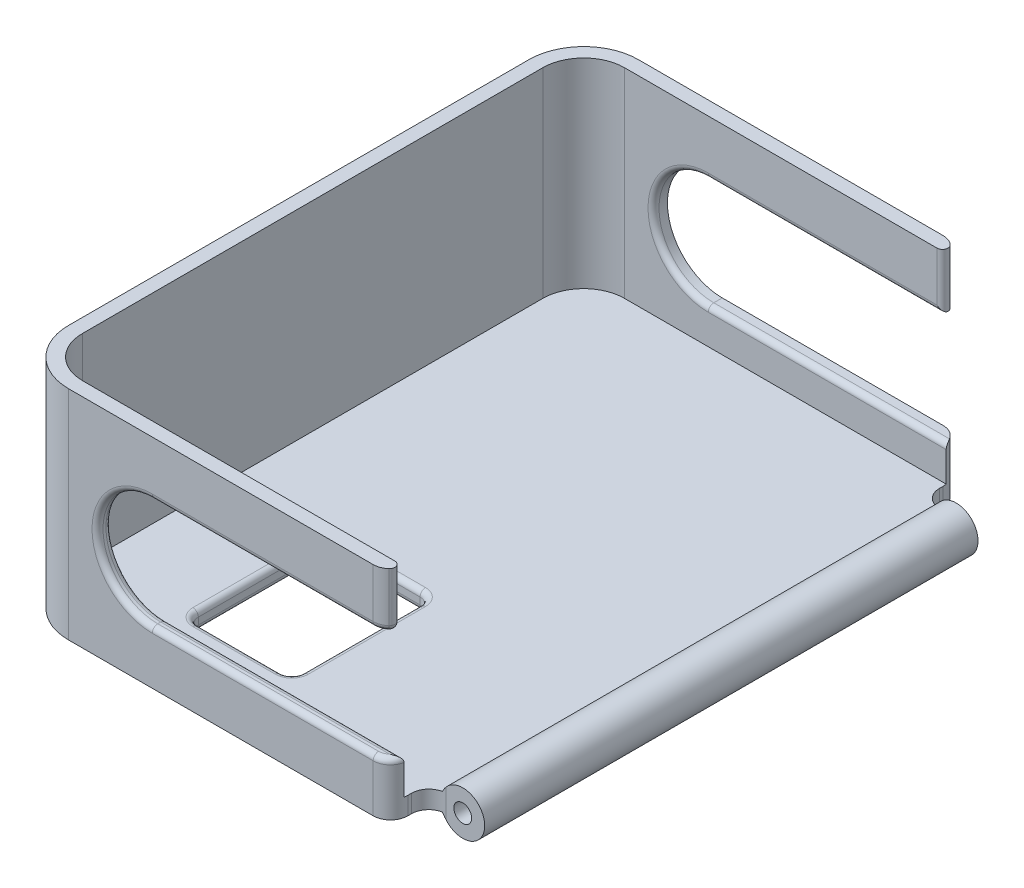
SolidWorks part; units mm, degrees
ref_plane "Front Plane" through (0, 0, 0) normal (0, 0, 1) x (1, 0, 0)
ref_plane "Top Plane" through (0, 0, 0) normal (0, 1, 0) x (1, 0, 0)
ref_plane "Right Plane" through (0, 0, 0) normal (1, 0, 0) x (0, 0, -1)
sketch "Sketch1" plane through (0, 0, 0) normal (0, 0, 1) x (1, 0, 0)
  circle A0 centre (0, 0) radius 4
  dimension "D1" = 8
extrude "Boss-Extrude1" add sketch "Sketch1" along normal mid plane 90
sketch "Sketch2" plane through (0, 0, 45) normal (0, 0, 1) x (1, 0, 0)
  circle A0 centre (0, 0) radius 1.625
  dimension "D1" = 3.25
extrude "Boss-Extrude2" add sketch "Sketch2" along normal blind 2
fillet "Fillet1" radius 1 1 edges at (1.625, 0, 47)
mirror "Mirror1" about plane through (0, 0, 0) normal (0, 0, 1) of "Fillet1", "Boss-Extrude2"
sketch "Sketch3" plane through (0, 0, 0) normal (0, 0, 1) x (1, 0, 0)
  line L0 (0, 0) -> (0, 1.625)
  line L1 (0, 1.625) -> (-74.93, 1.625)
  line L2 (-74.93, 1.625) -> (-74.93, -1.625)
  line L3 (-74.93, -1.625) -> (0, -1.625)
  line L4 (0, -1.625) -> (0, 0)
  circle A0 centre (0, 0) radius 1.625 construction
  dimension "D1" = 74.93
extrude "Boss-Extrude3" add sketch "Sketch3" along normal up to surface and the other way up to surface up to face at (1.625, 0, 45) other way up to face at (1.625, 0, -45)
sketch "Sketch5" plane through (0, 1.625, 0) normal (0, 1, 0) x (1, 0, 0)
  line L0 (-6.195, 45) -> (-6.195, 51.985)
  line L1 (-74.93, 45) -> (-3.655, 45) construction
  line L2 (-6.195, 51.985) -> (-74.93, 51.985)
  line L3 (-74.93, 51.985) -> (-74.93, 45)
  line L4 (-74.93, 45) -> (-6.195, 45)
  line L5 (-3.655, -45) -> (-3.655, 45) construction
  dimension "D1" = 2.54
  dimension "D2" = 6.985
extrude "Boss-Extrude4" add sketch "Sketch5" against normal up to surface (3.25 mm away) up to face at (-39.2925, -1.625, 0)
mirror "Mirror2" about plane through (0, 0, 0) normal (0, 0, 1) of "Boss-Extrude4"
fillet "Fillet2" radius 3.175 4 edges at (-6.195, 0, -51.985) (-6.195, 0, -45) (-6.195, 0, 51.985) (-6.195, 0, 45)
fillet "Fillet3" radius 10 2 edges at (-74.93, 0, -51.985) (-74.93, 0, 51.985)
sketch "Sketch6" plane through (0, 1.625, 0) normal (0, 1, 0) x (1, 0, 0)
  line L0 (-9.37, 49.445) -> (-64.93, 49.445)
  line L1 (-72.39, 41.985) -> (-72.39, -41.985)
  line L2 (-64.93, -49.445) -> (-9.37, -49.445)
  line L7 (-9.37, -49.445) -> (-6.2592, -49.445)
  line L8 (-9.37, 49.445) -> (-6.2592, 49.445)
  line L17 (-9.37, 51.985) -> (-64.93, 51.985)
  line L18 (-74.93, 41.985) -> (-74.93, -41.985)
  line L19 (-64.93, -51.985) -> (-9.37, -51.985)
  line L20 (-6.195, -48.81) -> (-6.195, -48.175)
  line L22 (-3.655, -45.0641) -> (-3.655, 45.0641)
  line L24 (-6.195, 48.175) -> (-6.195, 48.81)
  line L25 (-9.37, 51.985) -> (-64.93, 51.985)
  line L26 (-74.93, 41.985) -> (-74.93, -41.985)
  line L27 (-64.93, -51.985) -> (-9.37, -51.985)
  arc A4 (-64.93, 49.445) -> (-72.39, 41.985) centre (-64.93, 41.985) ccw
  arc A5 (-72.39, -41.985) -> (-64.93, -49.445) centre (-64.93, -41.985) ccw
  arc A6 (-9.37, -51.985) -> (-6.195, -48.81) centre (-9.37, -48.81) ccw construction
  arc A7 (-9.37, -51.985) -> (-6.2592, -49.445) centre (-9.37, -48.81) ccw
  arc A10 (-64.93, 51.985) -> (-74.93, 41.985) centre (-64.93, 41.985) ccw
  arc A11 (-74.93, -41.985) -> (-64.93, -51.985) centre (-64.93, -41.985) ccw
  arc A12 (-9.37, -51.985) -> (-6.195, -48.81) centre (-9.37, -48.81) ccw
  arc A13 (-3.655, -45.0641) -> (-6.195, -48.175) centre (-3.02, -48.175) ccw
  arc A14 (-6.195, 48.175) -> (-3.655, 45.0641) centre (-3.02, 48.175) ccw
  arc A15 (-6.195, 48.81) -> (-9.37, 51.985) centre (-9.37, 48.81) ccw
  arc A16 (-64.93, 51.985) -> (-74.93, 41.985) centre (-64.93, 41.985) ccw
  arc A17 (-74.93, -41.985) -> (-64.93, -51.985) centre (-64.93, -41.985) ccw
  arc A22 (-6.195, 48.81) -> (-9.37, 51.985) centre (-9.37, 48.81) ccw construction
  arc A23 (-6.2592, 49.445) -> (-9.37, 51.985) centre (-9.37, 48.81) ccw
  dimension "D1" = 0
  dimension "D2" = 2.54
extrude "Boss-Extrude5" add sketch "Sketch6" along normal blind 36.449
sketch "Sketch7" plane through (0, -1.625, 0) normal (0, -1, 0) x (1, 0, 0)
  line L0 (-64.93, 51.985) -> (-9.37, 51.985) construction
  line L1 (-54.455, 40.785) -> (-35.405, 40.785)
  line L2 (-54.455, 40.785) -> (-54.455, 15.385)
  line L3 (-54.455, 15.385) -> (-35.405, 15.385)
  line L4 (-35.405, 40.785) -> (-35.405, 15.385)
  line L5 (-54.455, 40.785) -> (-35.405, 15.385) construction
  line L6 (-54.455, 15.385) -> (-35.405, 40.785) construction
  line L7 (-3.655, -45.0641) -> (-3.655, 45.0641) construction
  point P0 (-44.93, 28.085)
  dimension "D1" = 25.4
  dimension "D2" = 11.2
  dimension "D3" = 19.05
  dimension "D4" = 31.75
extrude "Cut-Extrude1" cut sketch "Sketch7" against normal blind 33.782
fillet "Fillet4" radius 2 4 edges at (-35.405, 0, 15.385) (-54.455, 0, 15.385) (-54.455, 0, 40.785) (-35.405, 0, 40.785)
sketch "Sketch9" plane through (0, 0, -51.985) normal (0, 0, -1) x (-1, 0, 0)
  line L3 (37.15, -1.625) -> (37.15, 38.074) construction
  line L4 (64.93, -1.625) -> (9.37, -1.625) construction
  line L5 (9.37, 38.074) -> (64.93, 38.074) construction
  line L6 (49.65, 18.074) -> (24.65, 18.074) construction
  line L7 (49.65, 8.074) -> (24.65, 8.074)
  line L8 (49.65, 28.074) -> (24.65, 28.074)
  arc A1 (49.65, 8.074) -> (49.65, 28.074) centre (49.65, 18.074) ccw
  arc A2 (24.65, 28.074) -> (24.65, 8.074) centre (24.65, 18.074) ccw
  point P8 (37.15, 18.074)
  dimension "D1" = 25
  dimension "D3" = 20
  dimension "D2" = 10
extrude "Cut-Extrude2" cut sketch "Sketch9" against normal through all
sketch "Sketch12" plane through (0, 38.074, 0) normal (0, 1, 0) x (1, 0, 0)
  line L0 (-74.93, -9.9755) -> (-79.8215, -9.9755)
  line L1 (-74.93, 41.985) -> (-74.93, -41.985) construction
  line L2 (-77.8215, -7.9755) -> (-77.8215, 7.98)
  line L3 (-79.8215, 9.98) -> (-74.93, 9.98)
  line L4 (-74.93, 9.98) -> (-74.93, -9.9755)
  arc A0 (-77.8215, 7.98) -> (-79.8215, 9.98) centre (-79.8215, 7.98) ccw
  arc A1 (-79.8215, -9.9755) -> (-77.8215, -7.9755) centre (-79.8215, -7.9755) ccw
  dimension "D1" = 2
extrude "Boss-Extrude6" [suppressed] add sketch "Sketch12" along normal blind 6.35
sketch "Sketch13" plane through (0, 0, 0) normal (0, 0, 1) x (1, 0, 0)
  circle A0 centre (0, 0) radius 1.625 construction
  circle A1 centre (0, 0) radius 1.625
extrude "Cut-Extrude3" cut sketch "Sketch13" against normal through all both and the other way through all
sketch "Sketch14" plane through (0, 0, -51.985) normal (0, 0, -1) x (-1, 0, 0)
  line L0 (24.65, 28.074) -> (1.781, 28.074)
  line L1 (1.781, 28.074) -> (1.781, 8.074)
  line L2 (1.781, 8.074) -> (24.65, 8.074)
  line L3 (24.65, 8.074) -> (24.65, 28.074)
extrude "Cut-Extrude4" cut sketch "Sketch14" against normal through all
fillet "Fillet5" radius 1 29 edges at (-53.8693, 1.625, 40.1992) (-44.93, 1.625, 40.785) (-35.9908, 1.625, 40.1992) (-35.405, 1.625, 28.085) (-35.9908, 1.625, 15.9708) (-44.93, 1.625, 15.385) (-53.8693, 1.625, 15.9708) (-53.8693, -1.625, 40.1992) (-44.93, -1.625, 40.785) (-35.9908, -1.625, 40.1992) (-35.405, -1.625, 28.085) (-35.9908, -1.625, 15.9708) (-44.93, -1.625, 15.385) (-53.8693, -1.625, 15.9708) (-27.9546, 8.074, -49.445) (-59.65, 18.074, -49.445) (-27.9546, 8.074, 49.445) (-59.65, 18.074, 49.445) (-59.65, 18.074, 51.985) (-29.51, 8.074, 51.985) (-54.455, 1.625, 28.085) (-54.455, -1.625, 28.085) (-27.9546, 28.074, -49.445) (-27.9546, 28.074, 49.445) (-29.51, 28.074, 51.985) (-7.362, 8.074, 51.2693) (-7.362, 28.074, 51.2693) (-6.2592, 33.074, 49.445) (-6.2592, 33.074, -49.445)
